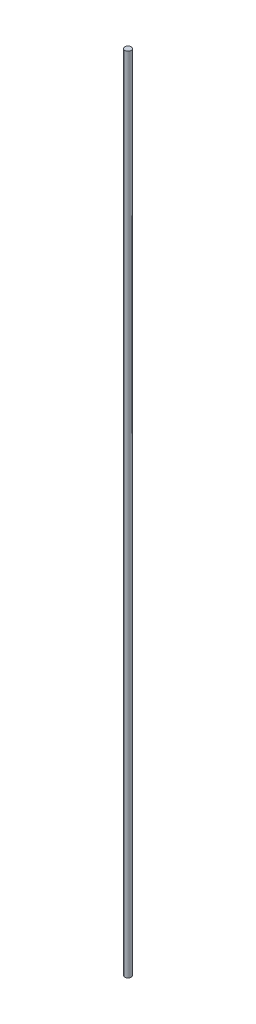
SolidWorks part; units mm, degrees
ref_plane "Front Plane" through (0, 0, 0) normal (0, 0, 1) x (1, 0, 0)
ref_plane "Top Plane" through (0, 0, 0) normal (0, 1, 0) x (1, 0, 0)
ref_plane "Right Plane" through (0, 0, 0) normal (1, 0, 0) x (0, 0, -1)
sketch "Sketch1" plane through (0, 0, 0) normal (0, 1, 0) x (1, 0, 0)
  circle A0 centre (0, 0) radius 3.175
  dimension "D1" = 6.35
extrude "Boss-Extrude1" add sketch "Sketch1" along normal mid plane 812.8
